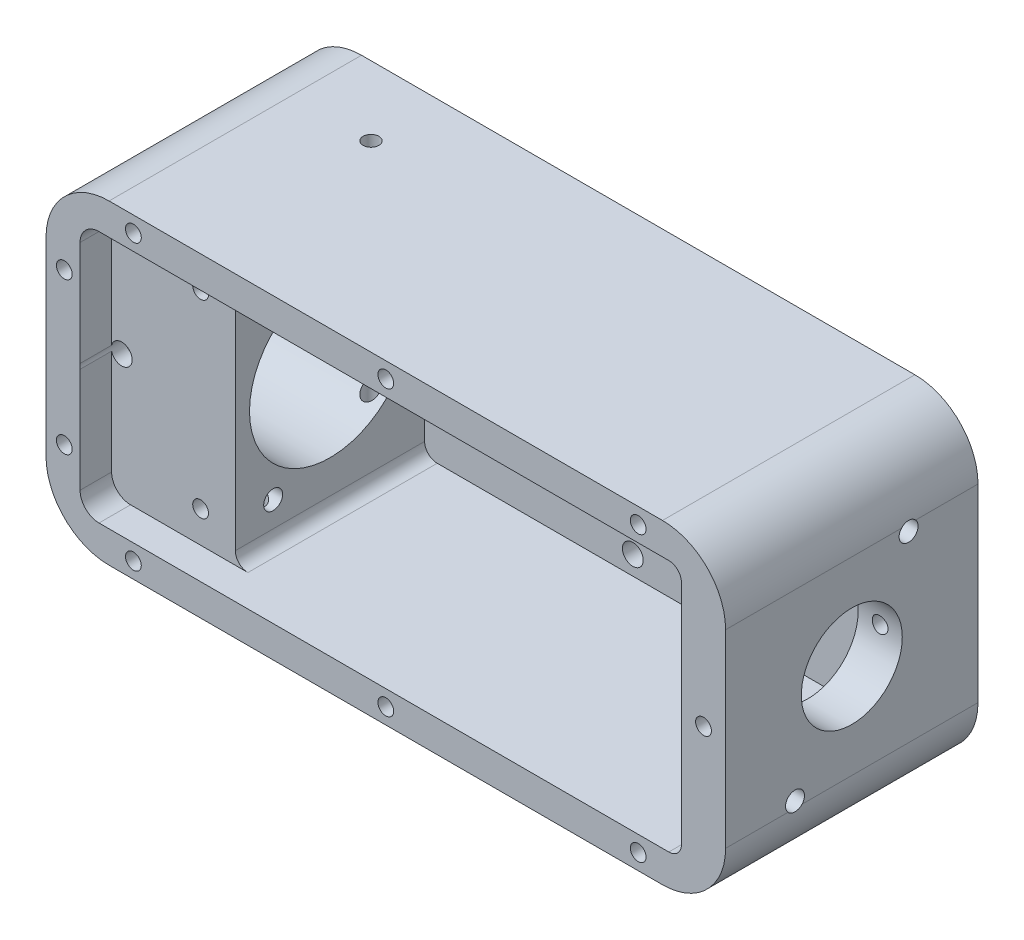
SolidWorks part; units mm, degrees
ref_plane "Front Plane" through (0, 0, 0) normal (0, 0, 1) x (1, 0, 0)
ref_plane "Top Plane" through (0, 0, 0) normal (0, 1, 0) x (1, 0, 0)
ref_plane "Right Plane" through (0, 0, 0) normal (1, 0, 0) x (0, 0, -1)
ref_plane "Plane1" through (0, 0, 40) normal (0, 0, 1) x (1, 0, 0)
sketch "Sketch1" plane through (0, 0, 40) normal (0, 0, 1) x (1, 0, 0)
  line L0 (0, 0) -> (0, -50)
  line L1 (0, -50) -> (107.7, -50)
  line L2 (107.7, -50) -> (107.7, 0)
  line L3 (107.7, 0) -> (0, 0)
extrude "Boss-Extrude1" add sketch "Sketch1" against normal blind 40
sketch "Sketch2" plane through (0, 0, 40) normal (0, 0, 1) x (1, 0, 0)
  line L0 (100.7, -5) -> (25, -5)
  line L1 (25, -5) -> (25, -45)
  line L2 (25, -45) -> (100.7, -45)
  line L3 (100.7, -45) -> (100.7, -5)
extrude "Cut-Extrude1" cut sketch "Sketch2" against normal blind 35
ref_plane "Plane2" through (0, 0, 35) normal (0, 0, -1) x (-1, 0, 0)
sketch "Sketch4" plane through (0, 0, 35) normal (0, 0, -1) x (-1, 0, 0)
  line L0 (-5.4, -45) -> (-5.4, -5)
  line L1 (-5.4, -5) -> (-25, -5)
  line L2 (-25, -5) -> (-25, -45)
  line L3 (-25, -45) -> (-5.4, -45)
extrude "Cut-Extrude2" cut sketch "Sketch4" against normal up to surface up to plane "Plane1"
sketch "Sketch5" plane through (0, 0, 0) normal (0, 0, -1) x (-1, 0, 0)
  line L0 (-99.7, -19.85) -> (-99.7, -30.15)
  line L1 (-99.7, -30.15) -> (-54.7, -30.15)
  line L2 (-54.7, -30.15) -> (-54.7, -19.85)
  line L3 (-54.7, -19.85) -> (-99.7, -19.85)
extrude "Cut-Extrude3" cut sketch "Sketch5" against normal through all
hole_wizard "#4 Clearance Hole1" positions "Sketch7" profile "Sketch6" hole size "#4" standard "ANSI Inch"
sketch "Sketch7" plane through (0, 0, 0) normal (0, 0, -1) x (-1, 0, 0)
  point P0 (-58, -42)
  point P1 (-78, -42)
  point P2 (-98, -42)
  point P3 (-98, -8)
  point P4 (-58, -8)
  point P5 (-78, -8)
sketch "Sketch6" plane through (58, -42, 0) normal (1, 0, 0) x (0, 1, 0)
  line L0 (0, 0) -> (0, 40)
  line L1 (0, 40) -> (1.65, 40)
  line L2 (1.65, 40) -> (1.65, 0)
  line L5 (1.65, 0) -> (0, 0)
  line L11 (0, -6.35) -> (0, 107.95) construction
  dimension "Thru Hole Dia." = 3.3
  dimension "Thru Hole Depth" = 40
hole_wizard "#4 Clearance Hole2" positions "Sketch9" profile "Sketch8" hole size "#4" standard "ANSI Inch"
sketch "Sketch9" plane through (0, 0, 0) normal (0, 0, -1) x (-1, 0, 0)
  point P0 (-8, -8)
sketch "Sketch8" plane through (8, -8, 0) normal (1, 0, 0) x (0, 1, 0)
  line L0 (0, 0) -> (0, 10)
  line L1 (0, 10) -> (1.65, 10)
  line L2 (1.65, 10) -> (1.65, 0)
  line L5 (1.65, 0) -> (0, 0)
  line L10 (0, 10) -> (-1.65, 10) construction
  line L11 (0, -6.35) -> (0, 107.95) construction
  dimension "Hole Dia." = 3.3
  dimension "Hole Depth" = 10
  dimension "Drill Angle" = 180
hole_wizard "#3 Clearance Hole1" positions "Sketch11" profile "Sketch10" hole size "#3" standard "ANSI Inch"
sketch "Sketch11" plane through (107.7, 0, 0) normal (1, 0, 0) x (0, 0, -1)
  point P0 (-29, -39)
sketch "Sketch10" plane through (107.7, -39, 29) normal (0, 1, 0) x (0, 0, -1)
  line L0 (0, 0) -> (0, 7)
  line L1 (0, 7) -> (1.5, 7)
  line L2 (1.5, 7) -> (1.5, 0)
  line L5 (1.5, 0) -> (0, 0)
  line L11 (0, -6.35) -> (0, 107.95) construction
  dimension "Thru Hole Dia." = 3
  dimension "Thru Hole Depth" = 7
hole_wizard "#3 Clearance Hole2" positions "Sketch13" profile "Sketch12" hole size "#3" standard "ANSI Inch"
sketch "Sketch13" plane through (100.7, 0, 0) normal (-1, 0, 0) x (0, 0, 1)
  point P0 (11, -11)
sketch "Sketch12" plane through (100.7, -11, 11) normal (0, 1, 0) x (0, 0, 1)
  line L0 (0, 0) -> (0, 7)
  line L1 (0, 7) -> (1.5, 7)
  line L2 (1.5, 7) -> (1.5, 0)
  line L5 (1.5, 0) -> (0, 0)
  line L11 (0, -6.35) -> (0, 107.95) construction
  dimension "Thru Hole Dia." = 3
  dimension "Thru Hole Depth" = 7
hole_wizard "#2 Clearance Hole1" positions "Sketch15" profile "Sketch14" hole size "#2" standard "ANSI Inch"
sketch "Sketch15" plane through (0, 0, 0) normal (0, 1, 0) x (1, 0, 0)
  point P0 (22.5, -11)
sketch "Sketch14" plane through (22.5, 0, 11) normal (1, 0, 0) x (0, 0, 1)
  line L0 (0, 0) -> (0, 50)
  line L1 (0, 50) -> (1.25, 50)
  line L2 (1.25, 50) -> (1.25, 0)
  line L5 (1.25, 0) -> (0, 0)
  line L11 (0, -6.35) -> (0, 107.95) construction
  dimension "Thru Hole Dia." = 2.5
  dimension "Thru Hole Depth" = 50
hole_wizard "Hole1" positions "Sketch17" profile "Sketch16" legacy
sketch "Sketch17" plane through (107.7, 0, 0) normal (1, 0, 0) x (0, 0, -1)
  point P0 (-20, -25)
sketch "Sketch16" plane through (107.7, -25, 20) normal (0, 1, 0) x (0, 0, -1)
  line L0 (0, 0) -> (0, 7)
  line L1 (0, 7) -> (8, 7)
  line L2 (8, 7) -> (8, 0)
  line L3 (8, 0) -> (0, 0)
  line L4 (0, 110) -> (0, -10) construction
  dimension "Diameter" = 16
  dimension "Depth" = 7
hole_wizard "#2 Clearance Hole2" positions "Sketch19" profile "Sketch18" hole size "#2" standard "ANSI Inch"
sketch "Sketch19" plane through (0, 0, 40) normal (0, 0, 1) x (1, 0, 0)
  point P0 (104.2, -25)
sketch "Sketch18" plane through (104.2, -25, 40) normal (1, 0, 0) x (0, -1, 0)
  line L0 (0, 0) -> (0, 52.0983)
  line L1 (0, 52.0983) -> (1.25, 52.0983)
  line L2 (1.25, 52.0983) -> (1.25, 0)
  line L5 (1.25, 0) -> (0, 0)
  line L10 (0, 52.0983) -> (-1.25, 52.0983) construction
  line L11 (0, -6.35) -> (0, 107.95) construction
  dimension "Hole Dia." = 2.5
  dimension "Hole Depth" = 52.0983
  dimension "Drill Angle" = 180
hole_wizard "#3 Clearance Hole3" positions "Sketch21" profile "Sketch20" hole size "#3" standard "ANSI Inch"
sketch "Sketch21" plane through (0, 0, 0) normal (-1, 0, 0) x (0, 0, 1)
  point P0 (29, -39)
  point P1 (11, -11)
sketch "Sketch20" plane through (0, -39, 29) normal (0, 1, 0) x (0, 0, 1)
  line L0 (0, 0) -> (0, 107.7)
  line L1 (0, 107.7) -> (1.5, 107.7)
  line L2 (1.5, 107.7) -> (1.5, 0)
  line L5 (1.5, 0) -> (0, 0)
  line L11 (0, -6.35) -> (0, 107.95) construction
  dimension "Thru Hole Dia." = 3
  dimension "Thru Hole Depth" = 107.7
hole_wizard "#2 Clearance Hole3" positions "Sketch23" profile "Sketch22" hole size "#2" standard "ANSI Inch"
sketch "Sketch23" plane through (0, 0, 40) normal (0, 0, 1) x (1, 0, 0)
  point P0 (2.9, -37)
  point P1 (93.85, -2.5)
  point P2 (53.85, -2.5)
  point P3 (13.85, -2.5)
  point P4 (2.9, -13)
  point P5 (13.85, -47.5)
  point P6 (53.85, -47.5)
  point P7 (93.85, -47.5)
sketch "Sketch22" plane through (2.9, -37, 40) normal (1, 0, 0) x (0, -1, 0)
  line L0 (0, 0) -> (0, 10)
  line L1 (0, 10) -> (1.25, 10)
  line L2 (1.25, 10) -> (1.25, 0)
  line L5 (1.25, 0) -> (0, 0)
  line L10 (0, 10) -> (-1.25, 10) construction
  line L11 (0, -6.35) -> (0, 107.95) construction
  dimension "Hole Dia." = 2.5
  dimension "Hole Depth" = 10
  dimension "Drill Angle" = 180
hole_wizard "#2 Clearance Hole4" positions "Sketch25" profile "Sketch24" hole size "#2" standard "ANSI Inch"
sketch "Sketch25" plane through (0, -50, 0) normal (0, -1, 0) x (-1, 0, 0)
  point P0 (-22.5, -29)
sketch "Sketch24" plane through (22.5, -50, 29) normal (1, 0, 0) x (0, 0, -1)
  line L0 (0, 0) -> (0, 9.5)
  line L1 (0, 9.5) -> (1.25, 9.5)
  line L2 (1.25, 9.5) -> (1.25, 0)
  line L5 (1.25, 0) -> (0, 0)
  line L11 (0, -6.35) -> (0, 107.95) construction
  dimension "Thru Hole Dia." = 2.5
  dimension "Thru Hole Depth" = 9.5
hole_wizard "1 (1) Diameter Hole1" positions "Sketch27" profile "Sketch26" hole size "1" standard "ANSI Inch"
sketch "Sketch27" plane through (25, 0, 0) normal (1, 0, 0) x (0, 0, -1)
  point P0 (-20, -25)
sketch "Sketch26" plane through (25, -25, 20) normal (0, 1, 0) x (0, 0, -1)
  line L0 (0, 0) -> (0, 25)
  line L1 (0, 25) -> (12.7, 25)
  line L2 (12.7, 25) -> (12.7, 0)
  line L5 (12.7, 0) -> (0, 0)
  line L11 (0, -6.35) -> (0, 107.95) construction
  dimension "Thru Hole Dia." = 25.4
  dimension "Thru Hole Depth" = 25
ref_plane "Plane3" through (0, 0, 32.5924) normal (0, 0, -1) x (-1, 0, 0)
hole_wizard "#4 Clearance Hole3" positions "Sketch29" profile "Sketch28" hole size "#4" standard "ANSI Inch"
sketch "Sketch29" plane through (0, 0, 32.5924) normal (0, 0, -1) x (-1, 0, 0)
  point P0 (-7, -25)
sketch "Sketch28" plane through (7, -25, 32.5924) normal (1, 0, 0) x (0, 1, 0)
  line L0 (0, 0) -> (0, 40)
  line L1 (0, 40) -> (1.65, 40)
  line L2 (1.65, 40) -> (1.65, 0)
  line L5 (1.65, 0) -> (0, 0)
  line L10 (0, 40) -> (-1.65, 40) construction
  line L11 (0, -6.35) -> (0, 107.95) construction
  dimension "Hole Dia." = 3.3
  dimension "Hole Depth" = 40
  dimension "Drill Angle" = 180
hole_wizard "#2 Clearance Hole5" positions "Sketch31" profile "Sketch30" hole size "#2" standard "ANSI Inch"
sketch "Sketch31" plane through (0, 0, 35) normal (0, 0, 1) x (1, 0, 0)
  point P0 (19.5, -10)
  point P1 (19.5, -40)
sketch "Sketch30" plane through (19.5, -10, 35) normal (1, 0, 0) x (0, -1, 0)
  line L0 (0, 0) -> (0, 10)
  line L1 (0, 10) -> (1.25, 10)
  line L2 (1.25, 10) -> (1.25, 0)
  line L5 (1.25, 0) -> (0, 0)
  line L10 (0, 10) -> (-1.25, 10) construction
  line L11 (0, -6.35) -> (0, 107.95) construction
  dimension "Hole Dia." = 2.5
  dimension "Hole Depth" = 10
  dimension "Drill Angle" = 180
fillet "Fillet1" radius 2 8 edges at (54.7, -19.85, 2.5) (54.7, -30.15, 2.5) (25, -45, 20) (100.7, -5, 22.5) (99.7, -30.15, 2.5) (100.7, -45, 22.5) (25, -5, 20) (99.7, -19.85, 2.5) tangent propagation no
fillet "Fillet2" radius 3 2 edges at (5.4, -5, 37.5) (5.4, -45, 37.5) tangent propagation no
fillet "Fillet3" radius 10 4 edges at (107.7, 0, 20) (107.7, -50, 20) (0, 0, 20) (0, -50, 20) tangent propagation no
sketch "草图1" plane through (0, 0, 0) normal (-1, 0, 0) x (0, 0, 1)
  circle A0 centre (20, -25) radius 12.75
  dimension "D1" = 25.5
extrude "切除-拉伸1" cut sketch "草图1" against normal up to surface (25 mm away) up to face at (25, -25, 7.3)
